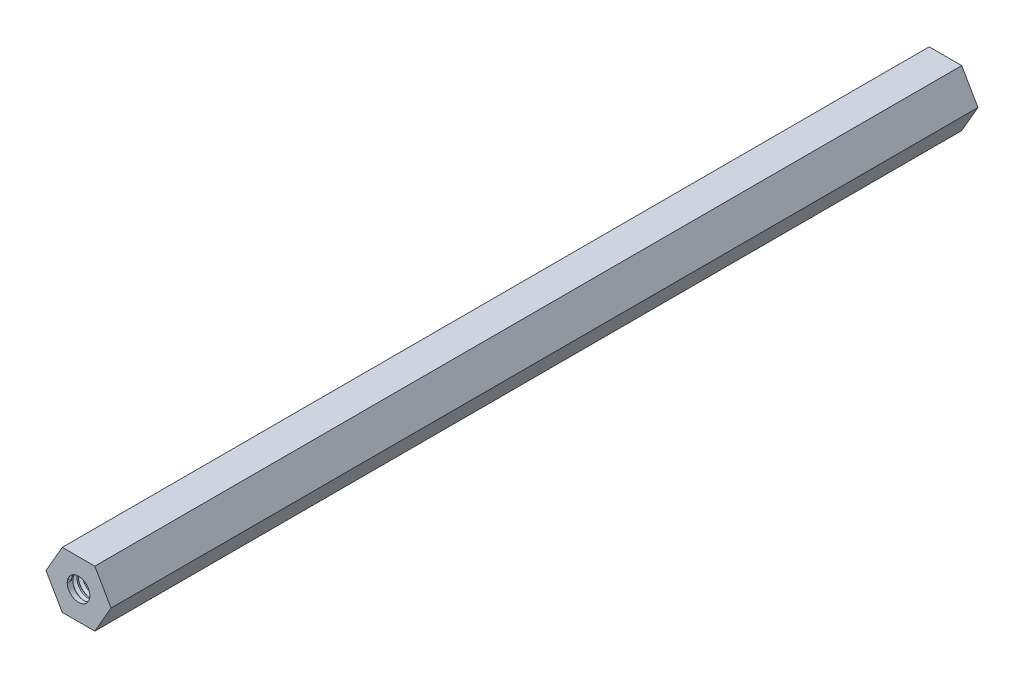
SolidWorks part; units mm, degrees
material "Acero inoxidable forjado"
ref_plane "Alzado" through (0, 0, 0) normal (0, 0, 1) x (1, 0, 0)
ref_plane "Planta" through (0, 0, 0) normal (0, 1, 0) x (1, 0, 0)
ref_plane "Vista lateral" through (0, 0, 0) normal (1, 0, 0) x (0, 0, -1)
sketch "Croquis2" plane through (0, 0, 0) normal (0, 0, 1) x (1, 0, 0)
  line L1 (3.6662, -6.35) -> (7.3323, 0)
  line L2 (7.3323, 0) -> (3.6662, 6.35)
  line L3 (3.6662, 6.35) -> (-3.6662, 6.35)
  line L4 (-3.6662, 6.35) -> (-7.3323, 0)
  line L5 (-7.3323, 0) -> (-3.6662, -6.35)
  line L6 (-3.6662, -6.35) -> (3.6662, -6.35)
  circle A0 centre (0, 0) radius 6.35 construction
  dimension "D1" = 12.7
extrude "Extrusión Hex Profile" add sketch "Croquis2" along normal mid plane 195.4063
sketch "Croquis3" plane through (0, 0, 0) normal (0, 0, 1) x (1, 0, 0)
  circle A0 centre (0, 0) radius 2.5527
  dimension "D1" = 5.1054
extrude "Tap Hole 1" cut sketch "Croquis3" against normal blind 19.05 from surface starting at face at (0, 0, 97.7032)
extrude "Tap Hole 2" cut sketch "Croquis3<3>" along normal blind 19.05 from surface starting at face at (0, 0, -97.7032)
sketch "Croquis3<3>" plane through (0, 0, 0) normal (0, 0, 1) x (1, 0, 0) same geometry as "Croquis3"
sketch "Croquis7" plane through (0, 0, 0) normal (0, 0, 1) x (1, 0, 0)
  circle A0 centre (0, 0) radius 6.8707
  dimension "D1" = 13.7414
extrude "ThunderHex" [suppressed] cut sketch "Croquis7" against normal through all both and the other way through all flip side to cut
sketch "Croquis8" plane through (0, 0, 0) normal (0, 1, 0) x (1, 0, 0)
  line L0 (0, -97.7032) -> (-5.5563, -97.7032) construction
  line L1 (3.6662, -97.7032) -> (-3.6662, -97.7032) construction
  line L3 (0, -97.7032) -> (0, 0) construction
  line L4 (-5.5563, -97.7032) -> (-6.35, -96.9094)
  line L5 (-6.35, -96.9094) -> (-6.35, -96.1157)
  line L6 (-6.35, -96.1157) -> (-5.9055, -96.1157)
  line L7 (-5.9055, -96.1157) -> (-5.9055, -94.5282)
  line L8 (-5.9055, -94.5282) -> (-12.7, -94.5282)
  line L9 (-12.7, -94.5282) -> (-12.7, -97.7032)
  line L10 (-12.7, -97.7032) -> (-5.5563, -97.7032)
  line L11 (-3.6662, -97.7032) -> (-7.3323, -97.7032) construction
  dimension "D1" = 11.811
  dimension "D2" = 12.7
  dimension "D3" = 45
  dimension "D4" = 0.7937
  dimension "D6" = 0.7937
  dimension "D7" = 3.175
  dimension "D8" = 25.4
revolve "Retaining Ring 1" [suppressed] cut sketch "Croquis8" angle 360 about L3
sketch "Croquis9" plane through (0, 0, 0) normal (0, -1, 0) x (1, 0, 0)
  line L0 (0, -97.7032) -> (-5.5563, -97.7032) construction
  line L3 (0, -97.7032) -> (0, 0) construction
  line L4 (-5.5563, -97.7032) -> (-6.35, -96.9094)
  line L5 (-6.35, -96.9094) -> (-6.35, -96.1157)
  line L6 (-6.35, -96.1157) -> (-5.9055, -96.1157)
  line L7 (-5.9055, -96.1157) -> (-5.9055, -94.5282)
  line L8 (-5.9055, -94.5282) -> (-12.7, -94.5282)
  line L9 (-12.7, -94.5282) -> (-12.7, -97.7032)
  line L10 (-12.7, -97.7032) -> (-5.5563, -97.7032)
  line L12 (-3.6662, -97.7032) -> (3.6662, -97.7032) construction
  line L13 (-7.3323, -97.7032) -> (-3.6662, -97.7032) construction
  dimension "D1" = 11.811
  dimension "D2" = 12.7
  dimension "D3" = 45
  dimension "D4" = 0.7937
  dimension "D6" = 0.7937
  dimension "D7" = 3.175
  dimension "D8" = 25.4
revolve "Retaining Ring 2" [suppressed] cut sketch "Croquis9" angle 360 about L3
sketch "Croquis10" plane through (0, 0, 0) normal (0, 1, 0) x (1, 0, 0)
  line L0 (0, -97.7032) -> (0, 0) construction
  line L1 (3.6662, -97.7032) -> (-3.6662, -97.7032) construction
  line L2 (0, -97.7032) -> (-5.5563, -97.7032) construction
  line L3 (-3.6662, -97.7032) -> (-7.3323, -97.7032) construction
  line L4 (-5.5563, -97.7032) -> (-6.35, -96.9094)
  line L5 (-6.35, -96.9094) -> (-6.35, -89.753)
  line L6 (-6.35, -89.753) -> (-9.525, -89.753)
  line L7 (-9.525, -89.753) -> (-9.525, -97.7032)
  line L8 (-9.525, -97.7032) -> (-5.5563, -97.7032)
  dimension "D2" = 12.7
  dimension "D1" = 45
  dimension "D3" = 0.7937
  dimension "D4" = 7.9502
  dimension "D5" = 19.05
revolve "Round End 1" [suppressed] cut sketch "Croquis10" angle 360 about L0
sketch "Croquis12" plane through (0, 0, 0) normal (0, -1, 0) x (1, 0, 0)
  line L0 (0, -97.7032) -> (0, 0) construction
  line L2 (0, -97.7032) -> (-5.5562, -97.7032) construction
  line L4 (-5.5562, -97.7032) -> (-6.35, -96.9094)
  line L5 (-6.35, -96.9094) -> (-6.35, -89.753)
  line L6 (-6.35, -89.753) -> (-9.525, -89.753)
  line L7 (-9.525, -89.753) -> (-9.525, -97.7032)
  line L8 (-9.525, -97.7032) -> (-5.5562, -97.7032)
  line L9 (-3.6662, -97.7032) -> (3.6662, -97.7032) construction
  dimension "D1" = 45
  dimension "D3" = 0.7937
  dimension "D4" = 7.9502
  dimension "D2" = 12.7
  dimension "D5" = 19.05
revolve "Round End 2" [suppressed] cut sketch "Croquis12" angle 360 about L0
thread "Rosca1" pitch 1.27 method cut profile "Perfil de rosca1" start angle 0, offset 0, length 0, pitch 1.27, diameter 5.1054
ref_plane "Plano1" through (-2.5527, 0, 97.7032) normal (0, -1, 0) x (-1, 0, 0)
sketch "Perfil de rosca1" plane through (-2.5527, 0, 97.7032) normal (0, -1, 0) x (-1, 0, 0)
  line L0 (0, 0) -> (0, 1.27) construction
  line L1 (0, 0) -> (0.6874, 0.3969)
  line L2 (0.6874, 0.3969) -> (0.6874, 0.5556)
  line L3 (0.6874, 0.5556) -> (0, 0.9525)
  line L4 (0.6874, 0.4762) -> (0, 0.4762) construction
  line L11 (0, 0) -> (0, 0.9525)
  point P2 (0, 0)
  dimension "Pitch" = 1.27
  dimension "Profile_Angle" = 60
  dimension "Profile_Land" = 0.1588
  dimension "Profile_Height" = 0.6874
thread "Rosca2" pitch 1.27 method cut profile "Perfil de rosca2" start angle 0, offset 0, length 0, pitch 1.27, diameter 5.1054
ref_plane "Plano2" through (2.5527, 0, -97.7032) normal (0, -1, 0) x (1, 0, 0)
sketch "Perfil de rosca2" plane through (2.5527, 0, -97.7032) normal (0, -1, 0) x (1, 0, 0)
  line L0 (0, 0) -> (0, 1.27) construction
  line L1 (0, 0) -> (0.6874, 0.3969)
  line L2 (0.6874, 0.3969) -> (0.6874, 0.5556)
  line L3 (0.6874, 0.5556) -> (0, 0.9525)
  line L4 (0.6874, 0.4762) -> (0, 0.4762) construction
  line L11 (0, 0) -> (0, 0.9525)
  point P2 (0, 0)
  dimension "Pitch" = 1.27
  dimension "Profile_Angle" = 60
  dimension "Profile_Land" = 0.1588
  dimension "Profile_Height" = 0.6874
equation "\"HexOD\"= 0.5pulgadas"
equation "\"Largo\"= 7.69316142pulgadas"
equation "\"D1@Croquis2\"=\"HexOD\""
equation "\"D1@Extrusión Hex Profile\" = \"Largo\""
equation "\"TapHole\"= IIF ( \"HexOD\" = 0.5pulgadas , 0.2010pulgadas , 0.190pulgadas )"
equation "\"D1@Croquis3\"=\"TapHole\""
equation "\"ProTapHole\"= 0.75pulgadas"
equation "\"D1@Tap Hole 1\" = \"ProTapHole\""
equation "\"D1@Tap Hole 2\" = \"ProTapHole\""
equation "\"ThunderHex\"= IIF ( \"HexOD\" = 0.5pulgadas , 0.541pulgadas , 0.4035pulgadas )"
equation "\"D1@Croquis7\"=\"ThunderHex\""
equation "\"D2@Croquis8\"=\"HexOD\""
equation "\"D1@Croquis8\"=if(\"HexOD\"=0.5pulgadas, 0.465pulgadas, 0.35pulgadas )"
equation "\"D2@Croquis9\"=\"HexOD\""
equation "\"D1@Croquis9\"=if(\"HexOD\"=0.5pulgadas, 0.465pulgadas, 0.35pulgadas )"
equation "\"D8@Croquis8\"=\"HexOD\"*2"
equation "\"D8@Croquis9\"=\"HexOD\"*2"
equation "\"D5@Croquis10\"=\"HexOD\"*1.5"
equation "\"D5@Croquis12\"=\"HexOD\"*1.5"
equation "\"D4@Croquis10\"=if( \"D2@Croquis10\"=<0.375, 0.28, 0.313)"
equation "\"D4@Croquis12\"=if( \"D2@Croquis10\"=<0.375, 0.28, 0.313)"
